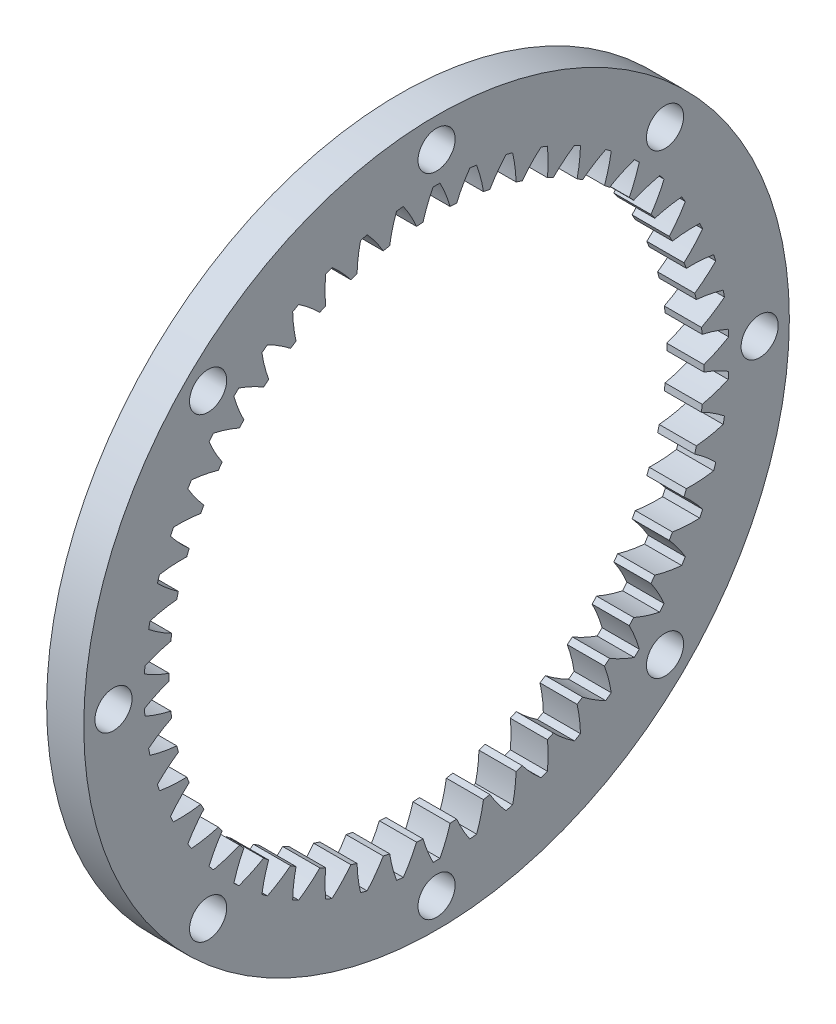
SolidWorks part; units mm, degrees
ref_plane "Plane1" through (0, 0, 0) normal (0, 0, 1) x (1, 0, 0)
ref_plane "Plane2" through (0, 0, 0) normal (0, 1, 0) x (1, 0, 0)
ref_plane "Plane3" through (0, 0, 0) normal (1, 0, 0) x (0, 0, -1)
other "Configuration Table"
sketch "HoldingSke" plane through (0, 0, 0) normal (0, 1, 0) x (1, 0, 0)
  line L0 (0, 0) -> (0.2143, -0.2553)
  line L1 (-15, 0) -> (100, 0) construction
  line L2 (0, 0) -> (-2.1039, 2.3779)
  line L3 (0, 0) -> (-11.863, 4.5341)
  line L4 (0, 0) -> (5.5511, 6.6156)
  line L5 (0, 0) -> (-23.7986, -8.8762)
  line L6 (0, 0) -> (-10.5278, -7.1032)
  line L7 (-2.1039, 2.3779) -> (3.3635, 27.1825)
  line L8 (-76.2, 5.3779) -> (-54.61, 5.3779)
  line L9 (-71.009, 38.7566) -> (-53.1078, 45.2721)
  line L10 (-76.2, 71.12) -> (104.1128, 71.12)
  line L11 (0, 0) -> (-20, 0)
  line L12 (-76.2, 101.6) -> (-76.093, 101.6)
  line L13 (24.9733, 27.94) -> (52.9518, 28.4284)
  line L14 (24.9733, 27.94) -> (24.9743, 27.94)
  line L15 (24.9733, 27.94) -> (100.4006, 29.5858)
  circle A0 centre (0, 0) radius 95
  circle A1 centre (0, 0) radius 12.7
  circle A2 centre (0, 0) radius 12.7
  dimension "Num_teeth" = 50
  dimension "Pitch_radius" = 180.3128
  dimension "Width" = 20
  dimension "Diameter" = 190
sketch "BasProSke" plane through (0, 0, 0) normal (0, 1, 0) x (1, 0, 0)
  line L0 (-10, 0) -> (60, 0) construction
  line L1 (0, 72) -> (0, 95)
  line L2 (0, 72) -> (20, 72)
  line L3 (20, 72) -> (20, 95)
  line L4 (20, 95) -> (0, 95)
  dimension "Thickness" = 20
  dimension "Diameter" = 190
revolve "Base-Revolve" add sketch "BasProSke" angle 360 about L0
sketch "TooCutSke" plane through (0, 0, 0) normal (1, 0, 0) x (0, 0, -1)
  line L3 (2.6233, 74.9541) -> (2.6233, 53.6633) construction
  line L4 (0, 0) -> (0, 59.563) construction
  line L5 (0, 0) -> (-4.2903, 68.1927) construction
  line L6 (-32.3866, 61.5171) -> (33.7854, 65.6803) construction
  circle A0 centre (0, 0) radius 75 construction
  circle A1 centre (0, 0) radius 78.751 construction
  circle A2 centre (0, 0) radius 63.4293 construction
  circle A3 centre (0, 0) radius 71.9746 construction
  arc A4 (3.6525, 71.8819) -> (0.9214, 78.7456) centre (-32.3866, 61.5171) ccw
  arc A5 (3.6525, 71.8819) -> (-3.6525, 71.8819) centre (0, 0) ccw
  arc A6 (0.9214, 78.7456) -> (-0.9214, 78.7456) centre (0, 0) ccw
  arc A7 (-0.9214, 78.7456) -> (-3.6525, 71.8819) centre (32.3866, 61.5171) ccw
extrude "ToothCut" cut sketch "TooCutSke" along normal through all
fillet "Breaks" [suppressed] radius 0.3
fillet "RootFillets" [suppressed] radius 0.751
pattern_circular "TeethCuts" count 50 every 7.2 about axis through (-10, 0, 0) along (1, 0, 0) of "RootFillets", "Breaks", "ToothCut"
sketch "Sketch1" plane through (20, 0, 0) normal (1, 0, 0) x (0, 0, -1)
  circle A0 centre (0, 87) radius 1.75
  circle A1 centre (0, 0) radius 95 construction
  dimension "D1" = 3.5
  dimension "D2" = 87
extrude "Cut-Extrude1" cut sketch "Sketch1" against normal through all
sketch "Sketch2" plane through (20, 0, 0) normal (1, 0, 0) x (0, 0, -1)
  circle A0 centre (0, 87) radius 5
extrude "Cut-Extrude2" cut sketch "Sketch2" against normal blind 7.5
pattern_circular "CirPattern1" count 8 over 360 about axis through (0, 0, 0) along (1, 0, 0) of "Cut-Extrude1", "Cut-Extrude2"
sketch "Sketch3" plane through (0, 0, 0) normal (0, 0, 1) x (1, 0, 0)
  line L0 (20, 95) -> (0, 95) construction
  line L1 (10, 95) -> (0, 95)
  line L2 (10, 95) -> (10, -95.2044)
  line L3 (10, -95.2044) -> (0, -95.2044)
  line L4 (0, 95) -> (0, -95.2044)
extrude "Cut-Extrude3" cut sketch "Sketch3" against normal through all both and the other way through all
equation "' \"Module@HoldingSke\" = 6.35"
equation "' \"Num_teeth@HoldingSke\" = 24"
equation "' \"Ap@HoldingSke\" =  14.5"
equation "' \"Ap@HoldingSke\" = 14.5"
equation "' \"Width@HoldingSke\" = 12"
equation "' \"Diameter@HoldingSke\" = 8 * 25.4"
equation "' \"Show_teeth@HoldingSke\" = 100"
equation "' \"Backlash@HoldingSke\" = 0.009 * 25.4"
equation "' \"Addendum_fac@HoldingSke\" = 1.0"
equation "' \"Dedendum_fac@HoldingSke\" = 1.25"
equation "' \"Dedendum_add@HoldingSke\" = 0.00005 * 25.4"
equation "' \"Clearance_fac@HoldingSke\" = 0.25"
equation "\"Pitch@HoldingSke\" = 1 / \"Module@HoldingSke\" "
equation "\"Overcut_dia@TooCutSke\" = (\"Num_teeth@HoldingSke\" - 2 * \"Addendum_fac@HoldingSke\") / \"Pitch@HoldingSke\" - 0.002 * 25.4"
equation "\"Pitch_dia@TooCutSke\" = \"Num_teeth@HoldingSke\" / \"Pitch@HoldingSke\""
equation "\"Base_dia@TooCutSke\" = \"Num_teeth@HoldingSke\" / \"Pitch@HoldingSke\" * cos((\"Ap@HoldingSke\"  * 3.14159265 / 180)) * 0.90"
equation "\"Root_dia@TooCutSke\" = \"Num_teeth@HoldingSke\"  / \"Pitch@HoldingSke\" + 2 *  \"Dedendum_fac@HoldingSke\"/ \"Pitch@HoldingSke\" + \"Dedendum_add@HoldingSke\" * 2"
equation "\"Half_ang@TooCutSke\" = 180 / \"Num_teeth@HoldingSke\""
equation "\"Half_CT@TooCutSke\" = \"Num_teeth@HoldingSke\" / \"Pitch@HoldingSke\" * sin((3.14159265 / 2 / \"Num_teeth@HoldingSke\")) / 2 + 10 * \"Backlash@HoldingSke\" / 4"
equation "\"Flank_rad@TooCutSke\" = \"Num_teeth@HoldingSke\" / \"Pitch@HoldingSke\" / 4"
equation "\"Radius@RootFillets\"= \"Clearance_fac@HoldingSke\" / \"Pitch@HoldingSke\" + \"Dedendum_add@HoldingSke\""
equation "\"Break_rad@Breaks\" = 0.02 / \"Pitch@HoldingSke\" * 5"
equation "\"Num_teeth@TeethCuts\" = int( \"Show_teeth@HoldingSke\" ) + 1"
equation "\"Num_teeth@TeethCuts\" = ((sgn( \"Num_teeth@TeethCuts\" - \"Num_teeth@HoldingSke\" )-1)*( \"Num_teeth@TeethCuts\" - \"Num_teeth@HoldingSke\" ))/-2+ \"Num_teeth@HoldingSke\""
equation "\"Num_teeth@TeethCuts\" = ((sgn( \"Num_teeth@TeethCuts\" - 2.0)+1)*( \"Num_teeth@TeethCuts\" - 2.0))/2 +2.0"
equation "\"Angle@TeethCuts\" = 360.0 / \"Num_teeth@HoldingSke\""
equation "\"Diameter@BasProSke\" = \"Num_teeth@HoldingSke\"  / \"Pitch@HoldingSke\" + 2 *  \"Dedendum_fac@HoldingSke\"/ \"Pitch@HoldingSke\" + \"Dedendum_add@HoldingSke\" * 2 + 0.002 * 25.4"
equation "\"Diameter@BasProSke\" = ((sgn( \"Diameter@BasProSke\"  - \"Diameter@HoldingSke\" )+1)*( \"Diameter@BasProSke\"  - \"Diameter@HoldingSke\" ))/2 + \"Diameter@HoldingSke\""
equation "\"Inside_diameter@BasProSke\" =  (\"Num_teeth@HoldingSke\" - 2 * \"Addendum_fac@HoldingSke\") / \"Pitch@HoldingSke\" "
equation "\"Thickness@BasProSke\"  = \"Width@HoldingSke\""
